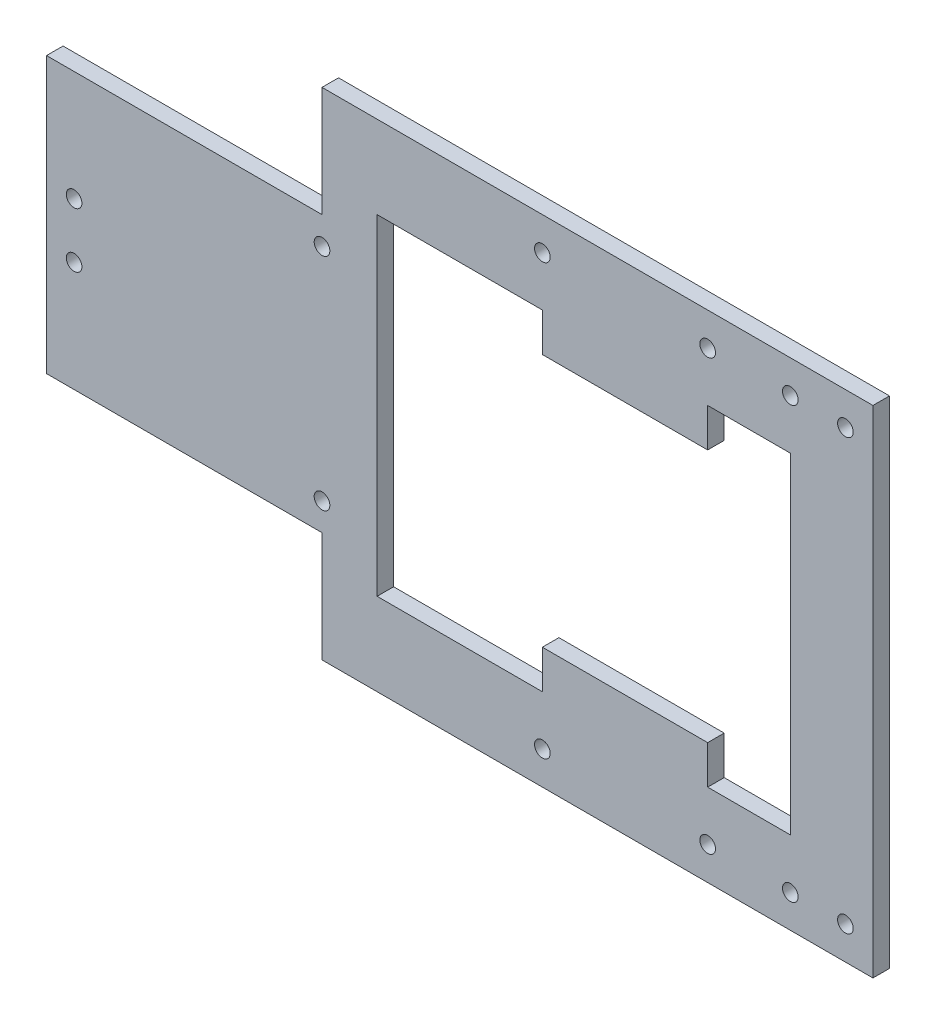
SolidWorks part; units mm, degrees
ref_plane "Front Plane" through (0, 0, 0) normal (0, 0, 1) x (1, 0, 0)
ref_plane "Top Plane" through (0, 0, 0) normal (0, 1, 0) x (1, 0, 0)
ref_plane "Right Plane" through (0, 0, 0) normal (1, 0, 0) x (0, 0, -1)
sketch "Sketch1" plane through (0, 0, 0) normal (0, 0, 1) x (1, 0, 0)
  line L0 (91.2766, 0) -> (-138.1947, 0) construction
  line L1 (0, 60.9532) -> (0, -61.5105) construction
  line L2 (-55, 45) -> (45, 45)
  line L3 (-105, 25) -> (-105, -25)
  line L4 (-55, -45) -> (45, -45)
  line L5 (45, 45) -> (45, -45)
  line L6 (-105, 25) -> (-55, 25)
  line L7 (-55, 25) -> (-55, 45)
  line L8 (-105, -25) -> (-55, -25)
  line L9 (-55, -25) -> (-55, -45)
  line L16 (-15, 30) -> (-45, 30)
  line L17 (-45, 30) -> (-45, -30)
  line L18 (-15, -30) -> (-45, -30)
  line L19 (-15, 30) -> (-15, 23)
  line L20 (15, 23) -> (-15, 23)
  line L21 (15, 23) -> (15, 30)
  line L22 (15, 30) -> (30.0001, 30)
  line L23 (30.0001, 30) -> (30.0001, -30)
  line L24 (-15, -30) -> (-15, -23)
  line L25 (15, -23) -> (-15, -23)
  line L26 (15, -30) -> (30.0001, -30)
  line L27 (15, -23) -> (15, -30)
  circle A1 centre (15, 39) radius 1.42
  circle A2 centre (-15, 39) radius 1.42
  circle A3 centre (-15, -39) radius 1.42
  circle A4 centre (15, -39) radius 1.42
  circle A6 centre (30.0001, 39.0563) radius 1.42
  circle A7 centre (40, 39.0133) radius 1.42
  circle A8 centre (-55, 20) radius 1.42
  circle A9 centre (-55, -20) radius 1.42
  circle A10 centre (40, -39.0133) radius 1.42
  circle A11 centre (30.0001, -39.0563) radius 1.42
  circle A12 centre (-100, 5) radius 1.42
  circle A13 centre (-100, -5) radius 1.42
  point P21 (-55, 35)
  point P31 (-55, -35)
  point P44 (-63, 0)
  point P45 (-93, 0)
  point P50 (-15, 0)
  point P51 (-45, 0)
  point P52 (22.5, 30)
  point P61 (22.5, -30)
  point P62 (30.0001, 0)
  dimension "D5" = 15
  dimension "D7" = 10
  dimension "D1" = 45
  dimension "D2" = 45
  dimension "D3" = 45
  dimension "D4" = 105
  dimension "D6" = 6
  dimension "D8" = 55
  dimension "D9" = 20
  dimension "D10" = 5
  dimension "D11" = 5
  dimension "D12" = 5
  dimension "D13" = 25
  dimension "D17" = 10
  dimension "D18" = 7
  dimension "D19" = 30
extrude "Boss-Extrude1" add sketch "Sketch1" along normal blind 3
